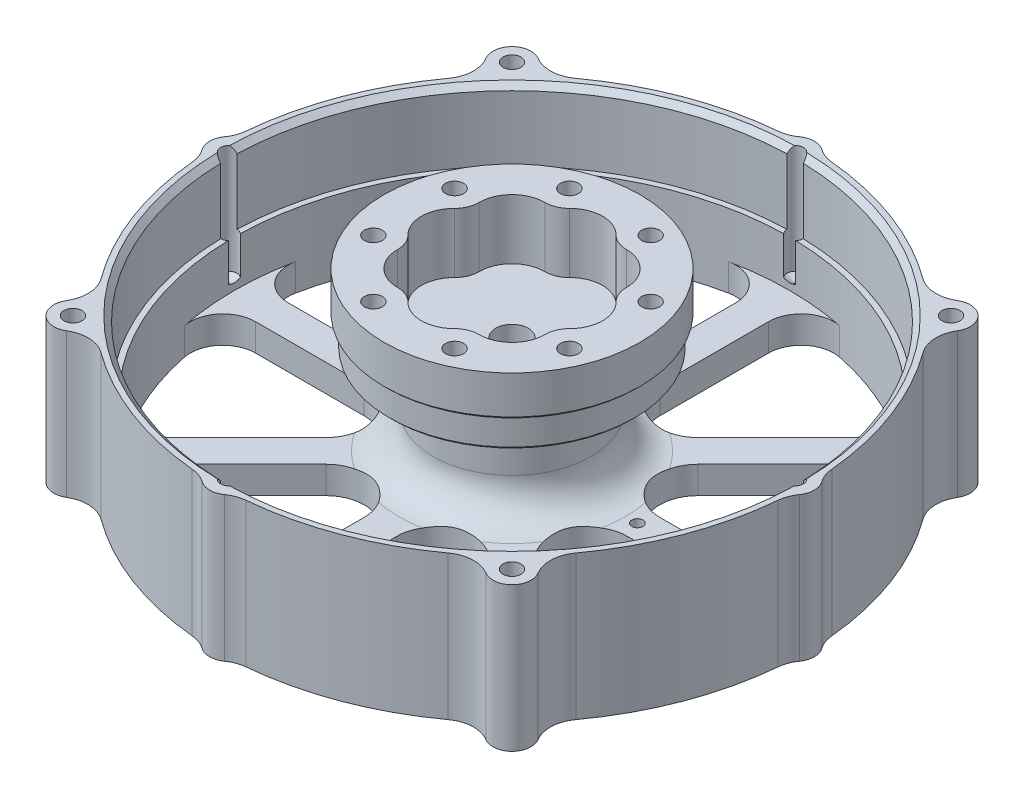
SolidWorks part; units mm, degrees
material "6061-T6 (SS)"
ref_plane "Front Plane" through (0, 0, 0) normal (0, 0, 1) x (1, 0, 0)
ref_plane "Top Plane" through (0, 0, 0) normal (0, 1, 0) x (1, 0, 0)
ref_plane "Right Plane" through (0, 0, 0) normal (1, 0, 0) x (0, 0, -1)
sketch "Sketch1" plane through (0, 0, 0) normal (0, 0, 1) x (1, 0, 0)
  line L0 (-23.5, 0) -> (-23.5, -7.5009)
  line L1 (-23.5, -7.5009) -> (-22.5, -7.5009)
  line L2 (-22.5, -7.5009) -> (-22.5, -13.0009)
  line L4 (-7.366, -13.0009) -> (-7.366, -13.5009)
  line L5 (-7.366, -13.5009) -> (-4.7625, -13.5009)
  line L6 (-4.7625, -13.5009) -> (-4.7625, -32.2642)
  line L7 (-4.7625, -32.2642) -> (-4.4704, -32.2642)
  line L8 (-4.4704, -32.2642) -> (-4.4704, -33.0008)
  line L9 (-4.4704, -33.0008) -> (-4.7625, -33.0008)
  line L10 (-4.7625, -33.0008) -> (-4.7625, -33.5008)
  line L12 (0, -34.0008) -> (0, 0) construction
  line L13 (0, 0) -> (-23.5, 0)
  line L14 (-3.175, -34.0008) -> (-4.2625, -34.0008)
  line L15 (-4.7625, -33.5008) -> (-4.2625, -34.0008)
  line L16 (-4.7625, -33.5008) -> (-4.7625, -34.0008) construction
  line L17 (-4.7625, -34.0008) -> (-4.2625, -34.0008) construction
  line L18 (-9, -20.6408) -> (-9, -25.1243)
  line L19 (-4.7625, -13.5009) -> (-11.1125, -13.5009)
  line L20 (-4.7625, -13.5009) -> (-4.7625, -20.6408)
  line L21 (-4.7625, -20.6408) -> (-11.1125, -20.6408)
  line L22 (-11.1125, -13.5009) -> (-11.1125, -20.6408)
  line L23 (-4.7625, -25.1243) -> (-11.1125, -25.1243)
  line L24 (-4.7625, -25.1243) -> (-4.7625, -32.2642)
  line L25 (-4.7625, -32.2642) -> (-11.1125, -32.2642)
  line L26 (-11.1125, -25.1243) -> (-11.1125, -32.2642)
  line L27 (-27.8003, -7.5009) -> (-22.4993, -7.5009)
  line L28 (-27.8003, -7.5009) -> (-27.8003, -22.5021)
  line L29 (-27.8003, -22.5021) -> (-22.4993, -22.5021)
  line L30 (-22.4993, -7.5009) -> (-22.4993, -22.5021)
  line L31 (-51.0007, -3) -> (-28.4988, -3)
  line L32 (-51.0007, -3) -> (-51.0007, -27.5008)
  line L33 (-51.0007, -27.5008) -> (-28.4988, -27.5008)
  line L34 (-28.4988, -3) -> (-28.4988, -27.5008)
  line L35 (-51.0007, -7.5009) -> (-52, -7.5009)
  line L36 (-51.0007, -7.5009) -> (-51.0007, -20.5006)
  line L37 (-51.0007, -20.5006) -> (-52, -20.5006)
  line L38 (-52, -7.5009) -> (-52, -20.5006)
  line L39 (-9, -20.6408) -> (-11.1125, -20.6408)
  line L40 (-7.366, -13.0009) -> (-18.5, -13.0009)
  line L42 (-18.5, -13.0009) -> (-22.5, -13.0009)
  line L43 (-9, -25.1243) -> (-11.1125, -25.1243)
  line L44 (-11.1125, -25.1243) -> (-11.1125, -32.2642)
  line L45 (-11.1125, -20.6408) -> (-11.1125, -13.5009)
  line L46 (-11.1125, -13.5009) -> (-14.5, -13.5009)
  line L47 (-14.5, -13.5009) -> (-14.5, -22.6508)
  line L49 (-20.85, -29.0008) -> (-51.0007, -29.0008)
  line L52 (-54, -7.5009) -> (-54, -34.0008)
  line L53 (-54, -34.0008) -> (-14.1125, -34.0008)
  line L54 (-51.0007, -29.0008) -> (-51.0007, -20.5006)
  line L55 (-51.0007, -20.5006) -> (-52, -20.5006)
  line L56 (-52, -20.5006) -> (-52, -7.5009)
  line L57 (-52, -7.5009) -> (-54, -7.5009)
  line L58 (0, 0) -> (0, -34.0008)
  line L59 (0, -34.0008) -> (0, -43.0001)
  line L60 (0, -43.0001) -> (-3.175, -43.0001)
  line L61 (-3.175, -43.0001) -> (-3.175, -34.0008)
  line L62 (-11.1125, -32.2642) -> (-14.1125, -32.2642)
  line L63 (-14.1125, -32.2642) -> (-14.1125, -34.0008)
  arc A0 (-20.85, -29.0008) -> (-14.5, -22.6508) centre (-20.85, -22.6508) ccw
  dimension "D33" = 6.35
  dimension "D1" = 1
  dimension "D2" = 45
  dimension "D3" = 9.525
  dimension "D4" = 7.366
  dimension "D5" = 0.5
  dimension "D6" = 0.7366
  dimension "D7" = 3
  dimension "D8" = 5.5
  dimension "D9" = 0.5
  dimension "D10" = 9.525
  dimension "D11" = 22.225
  dimension "D12" = 7.1399
  dimension "D13" = 51.0007
  dimension "D14" = 28.4988
  dimension "D15" = 44.9986
  dimension "D16" = 55.6006
  dimension "D17" = 15.0012
  dimension "D18" = 24.5008
  dimension "D19" = 4.5009
  dimension "D20" = 12.9997
  dimension "D21" = 52
  dimension "D22" = 4.5009
  dimension "D23" = 4
  dimension "D24" = 18
  dimension "D25" = 14.5
  dimension "D26" = 1.5
  dimension "D27" = 5
  dimension "D28" = 2
  dimension "D29" = 4.4704
  dimension "D30" = 0.5
  dimension "D31" = 8.9992
  dimension "D32" = 3.175
  dimension "D34" = 3
  dimension "D35" = 90
revolve "Revolve1" add sketch "Sketch1" angle 360 about L12
chamfer "Chamfer1" distance 0.5 angle 45 3 edges at (22.4993, -13.0009, 0) (23.5, -7.5009, 0) (3.175, -43.0001, 0)
sketch "Sketch2" plane through (0, 0, 0) normal (0, 1, 0) x (1, 0, 0)
  line L1 (-7.4558, 18) -> (-18, 7.4558) construction
  line L2 (-18, 7.4558) -> (-18, -7.4558) construction
  line L3 (-18, -7.4558) -> (-7.4558, -18) construction
  line L4 (-7.4558, -18) -> (7.4558, -18) construction
  line L5 (7.4558, -18) -> (18, -7.4558) construction
  line L6 (18, -7.4558) -> (18, 7.4558) construction
  line L7 (18, 7.4558) -> (7.4558, 18) construction
  line L8 (7.4558, 18) -> (-7.4558, 18) construction
  circle A0 centre (0, 0) radius 6.35 construction
  circle A1 centre (0, 0) radius 18 construction
  circle A2 centre (-7.4558, 18) radius 2 construction
  circle A3 centre (-18, 7.4558) radius 2 construction
  circle A4 centre (-18, -7.4558) radius 2 construction
  circle A5 centre (-7.4558, -18) radius 2 construction
  circle A6 centre (7.4558, -18) radius 2 construction
  circle A7 centre (18, -7.4558) radius 2 construction
  circle A8 centre (18, 7.4558) radius 2 construction
  circle A9 centre (7.4558, 18) radius 2 construction
  dimension "D1" = 12.7
  dimension "D2" = 4
  dimension "D3" = 18
hole_wizard "M4x0.7 Tapped Hole1" positions "Sketch3" profile "Sketch5" tap size "M4x0.7" standard "ANSI Metric"
sketch "Sketch3" plane through (0, 0, 0) normal (0, 1, 0) x (1, 0, 0)
  point P0 (-18, 7.4558)
  point P3 (-18, -7.4558)
  point P6 (-7.4558, -18)
  point P9 (7.4558, -18)
  point P12 (18, -7.4558)
  point P15 (18, 7.4558)
  point P18 (7.4558, 18)
  point P21 (-7.4558, 18)
cosmetic thread "Hole Thread1" parameters "D2"=4
cosmetic thread "Hole Thread2" parameters "D2"=4
cosmetic thread "Hole Thread3" parameters "D2"=4
cosmetic thread "Hole Thread4" parameters "D2"=4
cosmetic thread "Hole Thread5" parameters "D2"=4
cosmetic thread "Hole Thread6" parameters "D2"=4
cosmetic thread "Hole Thread7" parameters "D2"=4
cosmetic thread "Hole Thread8" parameters "D2"=4
sketch "Sketch5" plane through (-18, 0, -7.4558) normal (1, 0, 0) x (0, 0, 1)
  line L0 (0, 0) -> (0, 34.0008)
  line L1 (0, 34.0008) -> (1.65, 34.0008)
  line L2 (1.65, 34.0008) -> (1.65, 0)
  line L5 (1.65, 0) -> (0, 0)
  line L11 (0, -6.35) -> (0, 107.95) construction
  dimension "Thru Tap Drill Dia." = 3.3
  dimension "Thru Tap Drill Depth" = 34.0008
hole_wizard "Ø6.0 (6) Diameter Hole1" positions "Sketch6" profile "Sketch7" hole size "Ø6.0" standard "ANSI Metric"
sketch "Sketch6" plane through (0, 0, 0) normal (0, 1, 0) x (1, 0, 0)
  point P0 (0, 0)
sketch "Sketch7" plane through (0, 0, 0) normal (1, 0, 0) x (0, 0, 1)
  line L0 (0, 0) -> (0, 28.8026)
  line L1 (0, 28.8026) -> (3, 27)
  line L2 (3, 27) -> (3, 0)
  line L5 (3, 0) -> (0, 0)
  line L10 (0, 28.8026) -> (-3, 27) construction
  line L11 (0, -6.35) -> (0, 107.95) construction
  dimension "Hole Dia." = 6
  dimension "Hole Depth" = 27
  dimension "Drill Angle" = 118
chamfer "Chamfer2" distance 1 angle 45 1 edges at (52, -7.5009, 0)
sketch "Sketch8" plane through (0, -7.5009, 0) normal (0, 1, 0) x (1, 0, 0)
  line L0 (0, 52) -> (0, 0) construction
  line L1 (52, 0) -> (0, 0) construction
  line L2 (0, 0) -> (-52, 0) construction
  line L3 (0, -52) -> (0, 0) construction
  arc A0 (-1.4998, 51.9784) -> (1.4998, 51.9784) centre (0, 52) ccw
  circle A1 centre (0, 0) radius 52 construction
  circle A2 centre (0, 0) radius 52 construction
  arc A3 (-1.4998, 51.9784) -> (1.4998, 51.9784) centre (0, 0) cw construction
  arc A4 (-51.9784, 1.4998) -> (-51.9784, -1.4998) centre (-52, 0) cw
  arc A5 (-51.9784, 1.4998) -> (-51.9784, -1.4998) centre (0, 0) ccw construction
  arc A6 (-1.4998, -51.9784) -> (1.4998, -51.9784) centre (0, -52) cw
  arc A7 (-1.4998, -51.9784) -> (1.4998, -51.9784) centre (0, 0) ccw construction
  arc A8 (51.9784, 1.4998) -> (51.9784, -1.4998) centre (52, 0) ccw
  arc A9 (51.9784, 1.4998) -> (51.9784, -1.4998) centre (0, 0) cw construction
  circle A10 centre (0, 52) radius 1.5
  circle A11 centre (0, -52) radius 1.5
  circle A12 centre (52, 0) radius 1.5
  circle A13 centre (-52, 0) radius 1.5
  dimension "D1" = 1.5
hole_wizard "Ø3.0 (3) Diameter Hole1" positions "Sketch9" profile "Sketch10" hole size "Ø3.0" standard "ANSI Metric"
sketch "Sketch9" plane through (0, -7.5009, 0) normal (0, 1, 0) x (1, 0, 0)
  arc A0 (1.4998, 51.9784) -> (-1.4998, 51.9784) centre (0, 0) ccw construction
  arc A1 (-51.9784, 1.4998) -> (-51.9784, -1.4998) centre (0, 0) ccw construction
  point P0 (0, 52)
  point P5 (-52, 0)
  point P10 (0, -52)
  point P13 (52, 0)
sketch "Sketch10" plane through (0, -7.5009, -52) normal (1, 0, 0) x (0, 0, 1)
  line L0 (0, 0) -> (0, 20.9013)
  line L1 (0, 20.9013) -> (1.5, 20)
  line L2 (1.5, 20) -> (1.5, 0)
  line L5 (1.5, 0) -> (0, 0)
  line L10 (0, 20.9013) -> (-1.5, 20) construction
  line L11 (0, -6.35) -> (0, 107.95) construction
  dimension "Hole Dia." = 3
  dimension "Hole Depth" = 20
  dimension "Drill Angle" = 118
sketch "Sketch11" plane through (0, -34.0008, 0) normal (0, -1, 0) x (1, 0, 0)
  line L0 (-23.0125, 0) -> (23.0125, 0) construction
  circle A0 centre (23.0125, 0) radius 1.25 construction
  circle A1 centre (-23.0125, 0) radius 1.25 construction
  dimension "D1" = 2.5
  dimension "D2" = 46.025
hole_wizard "M2.5x0.45 Tapped Hole1" positions "Sketch12" profile "Sketch13" tap size "M2.5x0.45" standard "ANSI Metric"
sketch "Sketch12" plane through (0, -34.0008, 0) normal (0, -1, 0) x (-1, 0, 0)
  point P0 (-23.0125, 0)
  point P3 (23.0125, 0)
sketch "Sketch13" plane through (23.0125, -34.0008, 0) normal (1, 0, 0) x (0, 0, -1)
  line L0 (0, 0) -> (0, 5.6159)
  line L1 (0, 5.6159) -> (1.025, 5)
  line L2 (1.025, 5) -> (1.025, 0)
  line L5 (1.025, 0) -> (0, 0)
  line L10 (0, 5.6159) -> (-1.025, 5) construction
  line L11 (0, -6.35) -> (0, 107.95) construction
  dimension "Tap Drill Dia." = 2.05
  dimension "Tap Drill Depth" = 5
  dimension "Drill Angle" = 118
cosmetic thread "Hole Thread9" parameters "D1"=5, "D2"=2.5
cosmetic thread "Hole Thread10" parameters "D1"=5, "D2"=2.5
sketch "Sketch14" plane through (0, -34.0008, 0) normal (0, 1, 0) x (1, 0, 0)
  line L0 (-14.9497, 19.1924) -> (-33.8791, 38.1218)
  line L1 (-7.2426, 3) -> (-7.2426, -3) construction
  line L2 (-7.2426, -3) -> (-3, -7.2426) construction
  line L3 (-3, -7.2426) -> (3, -7.2426) construction
  line L4 (3, -7.2426) -> (7.2426, -3) construction
  line L5 (7.2426, -3) -> (7.2426, 3) construction
  line L6 (7.2426, 3) -> (3, 7.2426) construction
  line L7 (3, 7.2426) -> (-3, 7.2426) construction
  line L8 (-3, 7.2426) -> (-7.2426, 3) construction
  line L9 (-3, 50.9123) -> (-3, 24.1421)
  circle A0 centre (0, 0) radius 7.2426 construction
  circle A1 centre (0, 0) radius 51.0007 construction
  arc A2 (-33.8791, 38.1218) -> (-3, 50.9123) centre (0, 0) cw
  arc A3 (-1.1078, 50.9886) -> (-50.9886, 1.1078) centre (0, 0) ccw construction
  arc A4 (-14.9497, 19.1924) -> (-3, 24.1421) centre (-10, 24.1421) ccw
  dimension "D2" = 7
  dimension "D1" = 6
extrude "Cut-Extrude1" cut sketch "Sketch14" along normal blind 10
pattern_circular "CirPattern5" count 8 over 360 about axis through (0, 0, 0) along (0, 1, 0) of "Cut-Extrude1"
fillet "Fillet1" radius 6 16 edges at (-3, -31.5008, -50.9123) (-33.8791, -31.5008, -38.1218) (-33.8791, -31.5008, 38.1218) (-3, -31.5008, 50.9123) (3, -31.5008, 50.9123) (33.8791, -31.5008, 38.1218) (38.1218, -31.5008, 33.8791) (50.9123, -31.5008, 3) (50.9123, -31.5008, -3) (38.1218, -31.5008, -33.8791) (-50.9123, -31.5008, 3) (-38.1218, -31.5008, 33.8791) (-38.1218, -31.5008, -33.8791) (-50.9123, -31.5008, -3) (33.8791, -31.5008, -38.1218) (3, -31.5008, -50.9123)
sketch "Sketch15" plane through (0, -7.5009, 0) normal (0, 1, 0) x (1, 0, 0)
  line L0 (-40.3051, -40.3051) -> (-40.3051, 40.3051) construction
  line L1 (-40.3051, -40.3051) -> (40.3051, -40.3051) construction
  line L2 (-40.3051, 40.3051) -> (40.3051, 40.3051) construction
  line L3 (40.3051, -40.3051) -> (40.3051, 40.3051) construction
  line L4 (-40.3051, -40.3051) -> (40.3051, 40.3051) construction
  line L5 (-40.3051, 40.3051) -> (40.3051, -40.3051) construction
  arc A0 (-39.4042, 36.923) -> (-36.923, 39.4042) centre (-40.3051, 40.3051) cw
  circle A1 centre (0, 0) radius 54 construction
  arc A2 (-39.4042, -36.923) -> (-36.923, -39.4042) centre (0, 0) ccw
  arc A3 (36.923, 39.4042) -> (39.4042, 36.923) centre (40.3051, 40.3051) cw
  arc A4 (39.4042, -36.923) -> (36.923, -39.4042) centre (40.3051, -40.3051) cw
  arc A5 (-39.4042, -36.923) -> (-36.923, -39.4042) centre (-40.3051, -40.3051) ccw
  arc A6 (36.923, -39.4042) -> (39.4042, -36.923) centre (0, 0) ccw
  arc A7 (-36.923, 39.4042) -> (-39.4042, 36.923) centre (0, 0) ccw
  arc A8 (39.4042, 36.923) -> (36.923, 39.4042) centre (0, 0) ccw
  arc A9 (-53.9207, -2.9259) -> (-53.9207, 2.9259) centre (-52, 0) cw
  arc A10 (-2.9259, 53.9207) -> (2.9259, 53.9207) centre (0, 52) cw
  arc A11 (53.9207, -2.9259) -> (53.9207, 2.9259) centre (52, 0) ccw
  arc A12 (-2.9259, -53.9207) -> (2.9259, -53.9207) centre (0, -52) ccw
  arc A13 (-53.9207, -2.9259) -> (-53.9207, 2.9259) centre (0, 0) cw
  arc A14 (-2.9259, 53.9207) -> (2.9259, 53.9207) centre (0, 0) cw
  arc A15 (53.9207, 2.9259) -> (53.9207, -2.9259) centre (0, 0) cw
  arc A16 (-2.9259, -53.9207) -> (2.9259, -53.9207) centre (0, 0) ccw
  circle A17 centre (0, 52) radius 1.5 construction
  point P1 (0, 0)
  dimension "D2" = 3.5
  dimension "D3" = 2
  dimension "D1" = 114
extrude "Boss-Extrude1" add sketch "Sketch15" against normal up to surface (26.5 mm away) up to face at (14.6383, -34.0008, 35.3399)
hole_wizard "M4x0.7 Tapped Hole2" positions "Sketch17" profile "Sketch19" tap size "M4x0.7" standard "ANSI Metric" end condition through all
sketch "Sketch17" plane through (0, -7.5009, 0) normal (0, 1, 0) x (1, 0, 0)
  point P0 (-40.3051, 40.3051)
  point P3 (-40.3051, -40.3051)
  point P6 (40.3051, -40.3051)
  point P9 (40.3051, 40.3051)
sketch "Sketch19" plane through (-40.3051, -7.5009, -40.3051) normal (1, 0, 0) x (0, 0, 1)
  line L0 (0, 0) -> (0, 35.4992)
  line L1 (0, 35.4992) -> (1.65, 35.4992)
  line L2 (1.65, 35.4992) -> (1.65, 0)
  line L5 (1.65, 0) -> (0, 0)
  line L11 (0, -6.35) -> (0, 107.95) construction
  dimension "Thru Tap Drill Dia." = 3.3
  dimension "Thru Tap Drill Depth" = 35.4992
cosmetic thread "Hole Thread11" parameters "D1"=10, "D2"=4.3
cosmetic thread "Hole Thread12" parameters "D1"=10, "D2"=4.3
cosmetic thread "Hole Thread13" parameters "D1"=10, "D2"=4.3
cosmetic thread "Hole Thread14" parameters "D1"=10, "D2"=4.3
fillet "Fillet2" radius 6 16 edges at (36.923, -20.7509, -39.4042) (39.4042, -20.7509, -36.923) (39.4042, -20.7509, 36.923) (36.923, -20.7509, 39.4042) (-36.923, -20.7509, 39.4042) (-39.4042, -20.7509, 36.923) (-39.4042, -20.7509, -36.923) (-36.923, -20.7509, -39.4042) (-53.9207, -20.7509, 2.9259) (-53.9207, -20.7509, -2.9259) (53.9207, -20.7509, -2.9259) (53.9207, -20.7509, 2.9259) (2.9259, -20.7509, 53.9207) (-2.9259, -20.7509, 53.9207) (-2.9259, -20.7509, -53.9207) (2.9259, -20.7509, -53.9207)
sketch "Sketch23" plane through (0, 0, 0) normal (0, 1, 0) x (1, 0, 0)
  circle A0 centre (0, 0) radius 15
  dimension "D1" = 30
extrude "Cut-Extrude3" cut sketch "Sketch23" against normal offset from surface (11.0009 mm away) 2 up to face at (-16.35, -13.0009, -7.4558)
sketch "Sketch24" plane through (0, 0, 0) normal (0, 1, 0) x (1, 0, 0)
  circle A0 centre (-7.4558, 18) radius 4.4831 construction
  circle A2 centre (7.4558, 18) radius 4.4831 construction
  circle A3 centre (-7.4558, 18) radius 1.65 construction
  circle A4 centre (7.4558, 18) radius 1.65 construction
  circle A5 centre (0, 0) radius 15 construction
  arc A6 (-4.2674, 14.8486) -> (4.2674, 14.8486) centre (0, 10.6308) cw
  arc A7 (-4.2674, 14.8486) -> (-5.7403, 13.8582) centre (-7.4558, 18) cw
  arc A8 (-5.7403, 13.8582) -> (5.7403, 13.8582) centre (0, 0) cw
  arc A9 (5.7403, 13.8582) -> (4.2674, 14.8486) centre (7.4558, 18) cw
  dimension "D1" = 6
extrude "Cut-Extrude4" cut sketch "Sketch24" against normal up to surface (11.0009 mm away) up to face at (15, -11.0009, 0)
pattern_circular "CirPattern6" count 8 over 360 about axis through (0, 0, 0) along (0, 1, 0) of "Cut-Extrude4"
sketch "Sketch20" plane through (0, -7.5009, 0) normal (0, 1, 0) x (1, 0, 0)
  arc A0 (-1.1078, 50.9886) -> (-50.9886, 1.1078) centre (0, 0) ccw construction
  arc A1 (-1.1078, 50.9886) -> (-50.9886, 1.1078) centre (0, 0) ccw
  circle A2 centre (0, 0) radius 51.0007
  arc A16 (31.8623, 43.5981) -> (4.9479, 53.7728) centre (0, 0) ccw
  arc A17 (-38.4989, 43.303) -> (-31.8623, 43.5981) centre (-35.4025, 48.4423) ccw
  arc A18 (-38.4989, 43.303) -> (-43.303, 38.4989) centre (-40.3051, 40.3051) ccw
  arc A19 (-43.5981, 31.8623) -> (-43.303, 38.4989) centre (-48.4423, 35.4025) ccw
  arc A20 (-43.5981, 31.8623) -> (-53.7728, 4.9479) centre (0, 0) ccw
  arc A21 (-43.303, -38.4989) -> (-43.5981, -31.8623) centre (-48.4423, -35.4025) ccw
  arc A22 (-43.303, -38.4989) -> (-38.4989, -43.303) centre (-40.3051, -40.3051) ccw
  arc A23 (-31.8623, -43.5981) -> (-38.4989, -43.303) centre (-35.4025, -48.4423) ccw
  arc A24 (-31.8623, -43.5981) -> (-4.9479, -53.7728) centre (0, 0) ccw
  arc A25 (38.4989, -43.303) -> (31.8623, -43.5981) centre (35.4025, -48.4423) ccw
  arc A26 (38.4989, -43.303) -> (43.303, -38.4989) centre (40.3051, -40.3051) ccw
  arc A27 (43.5981, -31.8623) -> (43.303, -38.4989) centre (48.4423, -35.4025) ccw
  arc A28 (43.5981, -31.8623) -> (53.7728, -4.9479) centre (0, 0) ccw
  arc A29 (43.303, 38.4989) -> (43.5981, 31.8623) centre (48.4423, 35.4025) ccw
  arc A30 (43.303, 38.4989) -> (38.4989, 43.303) centre (40.3051, 40.3051) ccw
  arc A31 (31.8623, 43.5981) -> (38.4989, 43.303) centre (35.4025, 48.4423) ccw
  arc A32 (31.8623, 43.5981) -> (4.9479, 53.7728) centre (0, 0) ccw
  arc A33 (-38.4989, 43.303) -> (-31.8623, 43.5981) centre (-35.4025, 48.4423) ccw
  arc A34 (-38.4989, 43.303) -> (-43.303, 38.4989) centre (-40.3051, 40.3051) ccw
  arc A35 (-43.5981, 31.8623) -> (-43.303, 38.4989) centre (-48.4423, 35.4025) ccw
  arc A36 (-43.5981, 31.8623) -> (-53.7728, 4.9479) centre (0, 0) ccw
  arc A37 (-43.303, -38.4989) -> (-43.5981, -31.8623) centre (-48.4423, -35.4025) ccw
  arc A38 (-43.303, -38.4989) -> (-38.4989, -43.303) centre (-40.3051, -40.3051) ccw
  arc A39 (-31.8623, -43.5981) -> (-38.4989, -43.303) centre (-35.4025, -48.4423) ccw
  arc A40 (-31.8623, -43.5981) -> (-4.9479, -53.7728) centre (0, 0) ccw
  arc A41 (38.4989, -43.303) -> (31.8623, -43.5981) centre (35.4025, -48.4423) ccw
  arc A42 (38.4989, -43.303) -> (43.303, -38.4989) centre (40.3051, -40.3051) ccw
  arc A43 (43.5981, -31.8623) -> (43.303, -38.4989) centre (48.4423, -35.4025) ccw
  arc A44 (43.5981, -31.8623) -> (53.7728, -4.9479) centre (0, 0) ccw
  arc A45 (43.303, 38.4989) -> (43.5981, 31.8623) centre (48.4423, 35.4025) ccw
  arc A46 (43.303, 38.4989) -> (38.4989, 43.303) centre (40.3051, 40.3051) ccw
  arc A47 (31.8623, 43.5981) -> (38.4989, 43.303) centre (35.4025, 48.4423) ccw
  arc A59 (-4.9479, 53.7728) -> (-31.8623, 43.5981) centre (0, 0) ccw
  arc A60 (-4.9479, 53.7728) -> (-31.8623, 43.5981) centre (0, 0) ccw
  arc A61 (-54.8544, 2.0255) -> (-54.8544, -2.0255) centre (-52, 0) ccw
  arc A62 (-54.8544, 2.0255) -> (-54.8544, -2.0255) centre (-52, 0) ccw
  arc A63 (-53.7728, -4.9479) -> (-43.5981, -31.8623) centre (0, 0) ccw
  arc A64 (-53.7728, -4.9479) -> (-43.5981, -31.8623) centre (0, 0) ccw
  arc A65 (-2.0255, -54.8544) -> (2.0255, -54.8544) centre (0, -52) ccw
  arc A66 (-2.0255, -54.8544) -> (2.0255, -54.8544) centre (0, -52) ccw
  arc A67 (4.9479, -53.7728) -> (31.8623, -43.5981) centre (0, 0) ccw
  arc A68 (4.9479, -53.7728) -> (31.8623, -43.5981) centre (0, 0) ccw
  arc A69 (54.8544, -2.0255) -> (54.8544, 2.0255) centre (52, 0) ccw
  arc A70 (54.8544, -2.0255) -> (54.8544, 2.0255) centre (52, 0) ccw
  arc A71 (53.7728, 4.9479) -> (43.5981, 31.8623) centre (0, 0) ccw
  arc A72 (53.7728, 4.9479) -> (43.5981, 31.8623) centre (0, 0) ccw
  arc A73 (2.0255, 54.8544) -> (-2.0255, 54.8544) centre (0, 52) ccw
  arc A74 (2.0255, 54.8544) -> (-2.0255, 54.8544) centre (0, 52) ccw
  arc A79 (-53.7728, -4.9479) -> (-54.8544, -2.0255) centre (-59.7476, -5.4977) ccw
  arc A80 (-53.7728, -4.9479) -> (-54.8544, -2.0255) centre (-59.7476, -5.4977) ccw
  arc A81 (-2.0255, -54.8544) -> (-4.9479, -53.7728) centre (-5.4977, -59.7476) ccw
  arc A82 (-2.0255, -54.8544) -> (-4.9479, -53.7728) centre (-5.4977, -59.7476) ccw
  arc A83 (4.9479, -53.7728) -> (2.0255, -54.8544) centre (5.4977, -59.7476) ccw
  arc A84 (4.9479, -53.7728) -> (2.0255, -54.8544) centre (5.4977, -59.7476) ccw
  arc A85 (54.8544, -2.0255) -> (53.7728, -4.9479) centre (59.7476, -5.4977) ccw
  arc A86 (54.8544, -2.0255) -> (53.7728, -4.9479) centre (59.7476, -5.4977) ccw
  arc A91 (-54.8544, 2.0255) -> (-53.7728, 4.9479) centre (-59.7476, 5.4977) ccw
  arc A92 (-54.8544, 2.0255) -> (-53.7728, 4.9479) centre (-59.7476, 5.4977) ccw
  arc A93 (53.7728, 4.9479) -> (54.8544, 2.0255) centre (59.7476, 5.4977) ccw
  arc A94 (53.7728, 4.9479) -> (54.8544, 2.0255) centre (59.7476, 5.4977) ccw
  arc A95 (2.0255, 54.8544) -> (4.9479, 53.7728) centre (5.4977, 59.7476) ccw
  arc A96 (2.0255, 54.8544) -> (4.9479, 53.7728) centre (5.4977, 59.7476) ccw
  arc A97 (-4.9479, 53.7728) -> (-2.0255, 54.8544) centre (-5.4977, 59.7476) ccw
  arc A98 (-4.9479, 53.7728) -> (-2.0255, 54.8544) centre (-5.4977, 59.7476) ccw
  dimension "D1" = 0
extrude "Boss-Extrude3" [suppressed] add sketch "Sketch20" along normal blind 5 separate body
sketch "Sketch21" [suppressed] plane through (0, -0.5009, 0) normal (0, 1, 0) x (1, 0, 0)
  circle A0 centre (0, 0) radius 24.5 construction
  circle A1 centre (0, 0) radius 24.5 construction
  circle A2 centre (0, 0) radius 26.5
  arc A16 (33.4245, 44.9311) -> (38.9853, 44.0811) centre (37.0057, 49.7451) ccw
  arc A17 (33.4245, 44.9311) -> (-33.4245, 44.9311) centre (0, 0) ccw
  arc A18 (-38.9853, 44.0811) -> (-33.4245, 44.9311) centre (-37.0057, 49.7451) ccw
  arc A19 (-38.9853, 44.0811) -> (-44.0811, 38.9853) centre (-40.3051, 40.3051) ccw
  arc A20 (-44.9311, 33.4245) -> (-44.0811, 38.9853) centre (-49.7451, 37.0057) ccw
  arc A21 (-44.9311, 33.4245) -> (-44.9311, -33.4245) centre (0, 0) ccw
  arc A22 (-44.0811, -38.9853) -> (-44.9311, -33.4245) centre (-49.7451, -37.0057) ccw
  arc A23 (-44.0811, -38.9853) -> (-38.9853, -44.0811) centre (-40.3051, -40.3051) ccw
  arc A24 (-33.4245, -44.9311) -> (-38.9853, -44.0811) centre (-37.0057, -49.7451) ccw
  arc A25 (-33.4245, -44.9311) -> (33.4245, -44.9311) centre (0, 0) ccw
  arc A26 (38.9853, -44.0811) -> (33.4245, -44.9311) centre (37.0057, -49.7451) ccw
  arc A27 (38.9853, -44.0811) -> (44.0811, -38.9853) centre (40.3051, -40.3051) ccw
  arc A28 (44.9311, -33.4245) -> (44.0811, -38.9853) centre (49.7451, -37.0057) ccw
  arc A29 (44.9311, -33.4245) -> (44.9311, 33.4245) centre (0, 0) ccw
  arc A30 (44.0811, 38.9853) -> (44.9311, 33.4245) centre (49.7451, 37.0057) ccw
  arc A31 (44.0811, 38.9853) -> (38.9853, 44.0811) centre (40.3051, 40.3051) ccw
  arc A32 (33.4245, 44.9311) -> (38.9853, 44.0811) centre (37.0057, 49.7451) ccw
  arc A33 (33.4245, 44.9311) -> (-33.4245, 44.9311) centre (0, 0) ccw
  arc A34 (-38.9853, 44.0811) -> (-33.4245, 44.9311) centre (-37.0057, 49.7451) ccw
  arc A35 (-38.9853, 44.0811) -> (-44.0811, 38.9853) centre (-40.3051, 40.3051) ccw
  arc A36 (-44.9311, 33.4245) -> (-44.0811, 38.9853) centre (-49.7451, 37.0057) ccw
  arc A37 (-44.9311, 33.4245) -> (-44.9311, -33.4245) centre (0, 0) ccw
  arc A38 (-44.0811, -38.9853) -> (-44.9311, -33.4245) centre (-49.7451, -37.0057) ccw
  arc A39 (-44.0811, -38.9853) -> (-38.9853, -44.0811) centre (-40.3051, -40.3051) ccw
  arc A40 (-33.4245, -44.9311) -> (-38.9853, -44.0811) centre (-37.0057, -49.7451) ccw
  arc A41 (-33.4245, -44.9311) -> (33.4245, -44.9311) centre (0, 0) ccw
  arc A42 (38.9853, -44.0811) -> (33.4245, -44.9311) centre (37.0057, -49.7451) ccw
  arc A43 (38.9853, -44.0811) -> (44.0811, -38.9853) centre (40.3051, -40.3051) ccw
  arc A44 (44.9311, -33.4245) -> (44.0811, -38.9853) centre (49.7451, -37.0057) ccw
  arc A45 (44.9311, -33.4245) -> (44.9311, 33.4245) centre (0, 0) ccw
  arc A46 (44.0811, 38.9853) -> (44.9311, 33.4245) centre (49.7451, 37.0057) ccw
  arc A47 (44.0811, 38.9853) -> (38.9853, 44.0811) centre (40.3051, 40.3051) ccw
  dimension "D1" = 0
  dimension "D2" = 2
extrude "Boss-Extrude4" [suppressed] add sketch "Sketch21" along normal blind 2
sketch "Sketch22" [suppressed] plane through (0, 1.4991, 0) normal (0, 1, 0) x (1, 0, 0)
  arc A0 (-44.0811, 38.9853) -> (-44.0811, -38.9853) centre (-155.6246, 0) cw
  arc A1 (-38.9853, 44.0811) -> (38.9853, 44.0811) centre (0, 155.6246) ccw
  arc A2 (44.0811, 38.9853) -> (44.0811, -38.9853) centre (155.6246, 0) ccw
  arc A3 (38.9853, -44.0811) -> (-38.9853, -44.0811) centre (0, -155.6246) ccw
  arc A4 (-44.0811, -38.9853) -> (-38.9853, -44.0811) centre (-40.3051, -40.3051) ccw construction
  arc A6 (-38.9853, 44.0811) -> (-44.0811, 38.9853) centre (-40.3051, 40.3051) ccw construction
  arc A7 (44.0811, 38.9853) -> (38.9853, 44.0811) centre (40.3051, 40.3051) ccw construction
  arc A8 (38.9853, -44.0811) -> (44.0811, -38.9853) centre (40.3051, -40.3051) ccw construction
  arc A25 (33.4245, 44.9311) -> (-33.4245, 44.9311) centre (0, 0) ccw
  arc A26 (-38.9853, 44.0811) -> (-33.4245, 44.9311) centre (-37.0057, 49.7451) ccw
  arc A27 (-38.9853, 44.0811) -> (-44.0811, 38.9853) centre (-40.3051, 40.3051) ccw
  arc A28 (-44.9311, 33.4245) -> (-44.0811, 38.9853) centre (-49.7451, 37.0057) ccw
  arc A29 (-44.9311, 33.4245) -> (-44.9311, -33.4245) centre (0, 0) ccw
  arc A30 (-44.0811, -38.9853) -> (-44.9311, -33.4245) centre (-49.7451, -37.0057) ccw
  arc A31 (-44.0811, -38.9853) -> (-38.9853, -44.0811) centre (-40.3051, -40.3051) ccw
  arc A32 (-33.4245, -44.9311) -> (-38.9853, -44.0811) centre (-37.0057, -49.7451) ccw
  arc A33 (-33.4245, -44.9311) -> (33.4245, -44.9311) centre (0, 0) ccw
  arc A34 (38.9853, -44.0811) -> (33.4245, -44.9311) centre (37.0057, -49.7451) ccw
  arc A35 (38.9853, -44.0811) -> (44.0811, -38.9853) centre (40.3051, -40.3051) ccw
  arc A36 (44.9311, -33.4245) -> (44.0811, -38.9853) centre (49.7451, -37.0057) ccw
  arc A37 (44.9311, -33.4245) -> (44.9311, 33.4245) centre (0, 0) ccw
  arc A38 (44.0811, 38.9853) -> (44.9311, 33.4245) centre (49.7451, 37.0057) ccw
  arc A39 (44.0811, 38.9853) -> (38.9853, 44.0811) centre (40.3051, 40.3051) ccw
  arc A40 (33.4245, 44.9311) -> (38.9853, 44.0811) centre (37.0057, 49.7451) ccw
  arc A41 (33.4245, 44.9311) -> (-33.4245, 44.9311) centre (0, 0) ccw
  arc A42 (-38.9853, 44.0811) -> (-33.4245, 44.9311) centre (-37.0057, 49.7451) ccw
  arc A43 (-38.9853, 44.0811) -> (-44.0811, 38.9853) centre (-40.3051, 40.3051) ccw
  arc A44 (-44.9311, 33.4245) -> (-44.0811, 38.9853) centre (-49.7451, 37.0057) ccw
  arc A45 (-44.9311, 33.4245) -> (-44.9311, -33.4245) centre (0, 0) ccw
  arc A46 (-44.0811, -38.9853) -> (-44.9311, -33.4245) centre (-49.7451, -37.0057) ccw
  arc A47 (-44.0811, -38.9853) -> (-38.9853, -44.0811) centre (-40.3051, -40.3051) ccw
  arc A48 (-33.4245, -44.9311) -> (-38.9853, -44.0811) centre (-37.0057, -49.7451) ccw
  arc A49 (-33.4245, -44.9311) -> (33.4245, -44.9311) centre (0, 0) ccw
  arc A50 (38.9853, -44.0811) -> (33.4245, -44.9311) centre (37.0057, -49.7451) ccw
  arc A51 (38.9853, -44.0811) -> (44.0811, -38.9853) centre (40.3051, -40.3051) ccw
  arc A52 (44.9311, -33.4245) -> (44.0811, -38.9853) centre (49.7451, -37.0057) ccw
  arc A53 (44.9311, -33.4245) -> (44.9311, 33.4245) centre (0, 0) ccw
  arc A54 (44.0811, 38.9853) -> (44.9311, 33.4245) centre (49.7451, 37.0057) ccw
  arc A55 (44.0811, 38.9853) -> (38.9853, 44.0811) centre (40.3051, 40.3051) ccw
  arc A56 (33.4245, 44.9311) -> (38.9853, 44.0811) centre (37.0057, 49.7451) ccw
  arc M18 (33.4245, 44.9311) -> (-33.4245, 44.9311) centre (0, 0) ccw
  arc M19 (-33.4245, 44.9311) -> (-38.9853, 44.0811) centre (-37.0057, 49.7451) cw
  arc M21 (-44.0811, 38.9853) -> (-44.9311, 33.4245) centre (-49.7451, 37.0057) cw
  arc M22 (-44.9311, 33.4245) -> (-44.9311, -33.4245) centre (0, 0) ccw
  arc M23 (-44.9311, -33.4245) -> (-44.0811, -38.9853) centre (-49.7451, -37.0057) cw
  arc M25 (-38.9853, -44.0811) -> (-33.4245, -44.9311) centre (-37.0057, -49.7451) cw
  arc M26 (-33.4245, -44.9311) -> (33.4245, -44.9311) centre (0, 0) ccw
  arc M27 (33.4245, -44.9311) -> (38.9853, -44.0811) centre (37.0057, -49.7451) cw
  arc M29 (44.0811, -38.9853) -> (44.9311, -33.4245) centre (49.7451, -37.0057) cw
  arc M30 (44.9311, -33.4245) -> (44.9311, 33.4245) centre (0, 0) ccw
  arc M31 (44.9311, 33.4245) -> (44.0811, 38.9853) centre (49.7451, 37.0057) cw
  arc M33 (38.9853, 44.0811) -> (33.4245, 44.9311) centre (37.0057, 49.7451) cw
  dimension "D1" = 0
extrude "Cut-Extrude2" [suppressed] cut sketch "Sketch22" against normal up to next contours A0 M21 M22 M23 | A1 M19 M33 M18 | A3 M27 M25 M26 | A2 M31 M29 M30
split "Split1" bodies to split 116 128 120 resulting bodies 105 106
